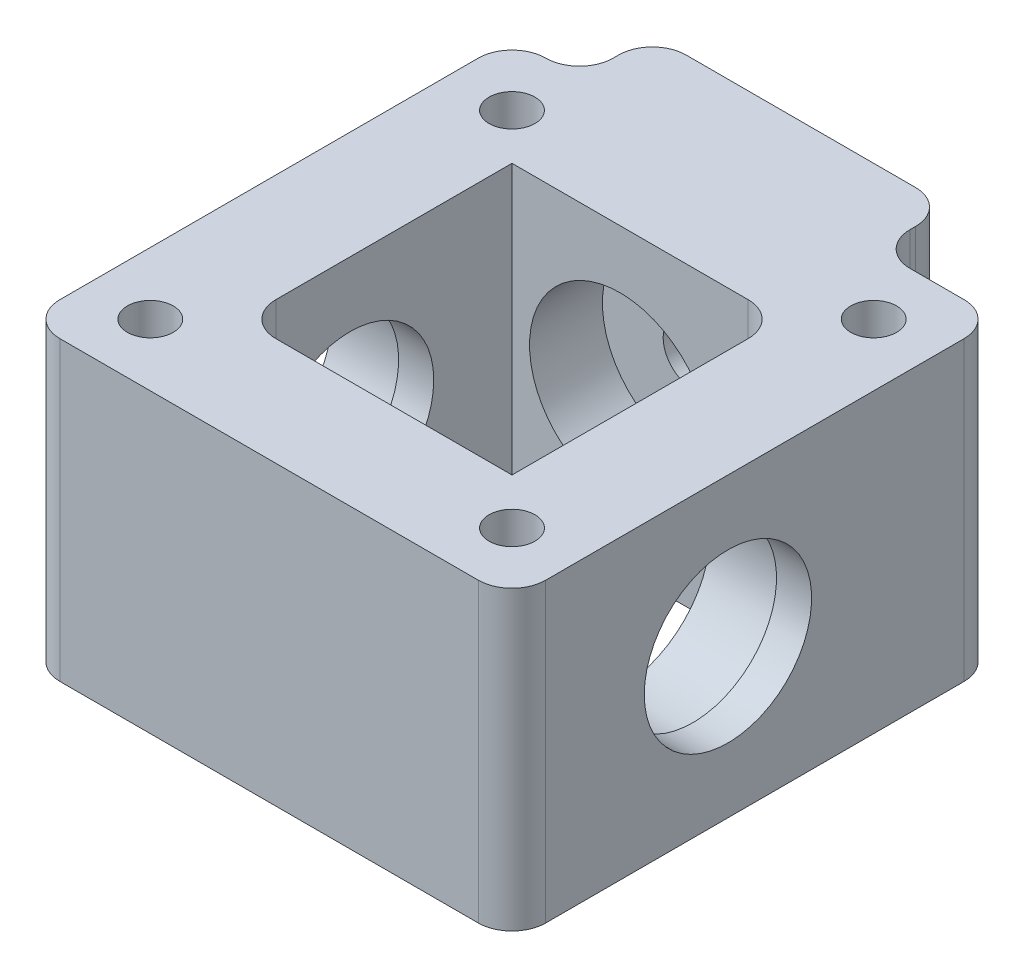
SolidWorks part; units mm, degrees
ref_plane "Front" through (0, 0, 0) normal (0, 0, 1) x (1, 0, 0)
ref_plane "Top" through (0, 0, 0) normal (0, 1, 0) x (1, 0, 0)
ref_plane "Right" through (0, 0, 0) normal (1, 0, 0) x (0, 0, -1)
sketch "Sketch3" plane through (0, 0, 0) normal (0, 1, 0) x (1, 0, 0)
  line L0 (8, -8) -> (28, -8)
  line L1 (0, 0) -> (36, 0)
  line L2 (0, 0) -> (0, -36)
  line L3 (0, -36) -> (36, -36)
  line L4 (36, 0) -> (36, -36)
  line L5 (28, -8) -> (28, -28)
  line L6 (8, -28) -> (28, -28)
  line L7 (8, -8) -> (8, -28)
  dimension "D1" = 36
  dimension "D2" = 36
  dimension "D3" = 8
extrude "Boss-Extrude1" add sketch "Sketch3" along normal blind 22
sketch "Sketch4" plane through (0, 0, 0) normal (0, 0, -1) x (-1, 0, 0)
  line L0 (0, 22) -> (0, 0) construction
  line L1 (-36, 0) -> (0, 0) construction
  circle A0 centre (-16, 11) radius 2.2
  point P6 (-16.8599, 4.6014)
  point P7 (-18.5572, 4.7986)
  point P8 (-18.5017, 4.1301)
  dimension "D1" = 4.4
  dimension "D2" = 16
  dimension "D3" = 11
extrude "Cut-Extrude1" cut sketch "Sketch4" against normal up to next
sketch "Sketch5" plane through (36, 0, 0) normal (1, 0, 0) x (0, 0, -1)
  line L0 (-36, 0) -> (0, 0) construction
  line L1 (0, 22) -> (0, 0) construction
  circle A0 centre (-20, 11) radius 6.2
  dimension "D1" = 12.4
  dimension "D2" = 11
  dimension "D3" = 20
extrude "Cut-Extrude2" cut sketch "Sketch5" against normal through all and the other way through all
sketch "Sketch6" plane through (0, 0, 0) normal (0, 0, -1) x (-1, 0, 0)
  line L0 (-36, 0) -> (0, 0) construction
  line L1 (-5, 0) -> (-27, 0)
  line L2 (-5, 0) -> (-5, 22)
  line L3 (-5, 22) -> (-27, 22)
  line L4 (-27, 0) -> (-27, 22)
  line L5 (-36, 22) -> (0, 22) construction
  line L6 (0, 22) -> (0, 0) construction
  circle A0 centre (-16, 11) radius 6.7
  dimension "D3" = 13.4
  dimension "D2" = 9
extrude "Boss-Extrude2" add sketch "Sketch6" along normal blind 5.4
sketch "Sketch7" plane through (0, 0, 8) normal (0, 0, 1) x (1, 0, 0)
  circle A0 centre (16, 11) radius 6.7
  dimension "D1" = 13.4
extrude "Cut-Extrude3" cut sketch "Sketch7" against normal blind 5.4
sketch "Sketch8" plane through (28, 0, 0) normal (-1, 0, 0) x (0, 0, 1)
  circle A0 centre (20, 11) radius 6.7
  dimension "D1" = 13.4
extrude "Cut-Extrude4" cut sketch "Sketch8" against normal blind 5.4
sketch "Sketch9" plane through (0, 0, 0) normal (-1, 0, 0) x (0, 0, 1)
  circle A0 centre (20, 11) radius 6.7
  dimension "D1" = 13.4
extrude "Cut-Extrude5" cut sketch "Sketch9" against normal blind 5.4
fillet "Fillet2" radius 2.5 4 edges at (27, 11, -5.4) (5, 11, -5.4) (5, 11, 0) (27, 11, 0)
fillet "Fillet3" radius 2.5 2 edges at (8, 11, 28) (28, 11, 8)
fillet "Fillet4" radius 2.5 4 edges at (0, 11, 0) (0, 11, 36) (36, 11, 36) (36, 11, 0)
sketch "Sketch10" plane through (0, 0, 0) normal (0, -1, 0) x (-1, 0, 0)
  line L0 (-36, -33.5) -> (-36, -2.5) construction
  line L1 (-33.5, 0) -> (-29.5, 0) construction
  circle A0 centre (-31.4, -4.6) radius 1.7
  circle A1 centre (-4.6, -4.6) radius 1.7
  circle A2 centre (-4.6, -31.4) radius 1.7
  circle A3 centre (-31.4, -31.4) radius 1.7
  dimension "D1" = 3.4
  dimension "D2" = 4.6
  dimension "D3" = 4.6
  dimension "D4" = 2
  dimension "D5" = 2
extrude "Cut-Extrude6" cut sketch "Sketch10" against normal through all
equation "\"v\"= 0.1"
equation "\"0ffset\"= 0.4"
equation "\"D1@Sketch4\"=\"0ffset\"+4"
equation "\"D3@Sketch6\"=\"0ffset\"+13"
equation "\"D1@Sketch7\"=\"0ffset\"+13"
equation "\"D1@Cut-Extrude3\"=\"0ffset\"+5"
equation "\"D1@Sketch8\"=\"0ffset\"+13"
equation "\"D1@Cut-Extrude4\"=\"0ffset\"+5"
equation "\"D1@Sketch9\"=\"0ffset\"+13"
equation "\"D1@Cut-Extrude5\"=\"0ffset\"+5"
equation "\"D1@Boss-Extrude2\"=\"0ffset\"+5"
equation "\"D1@Sketch10\"=\"0ffset\"+3"
